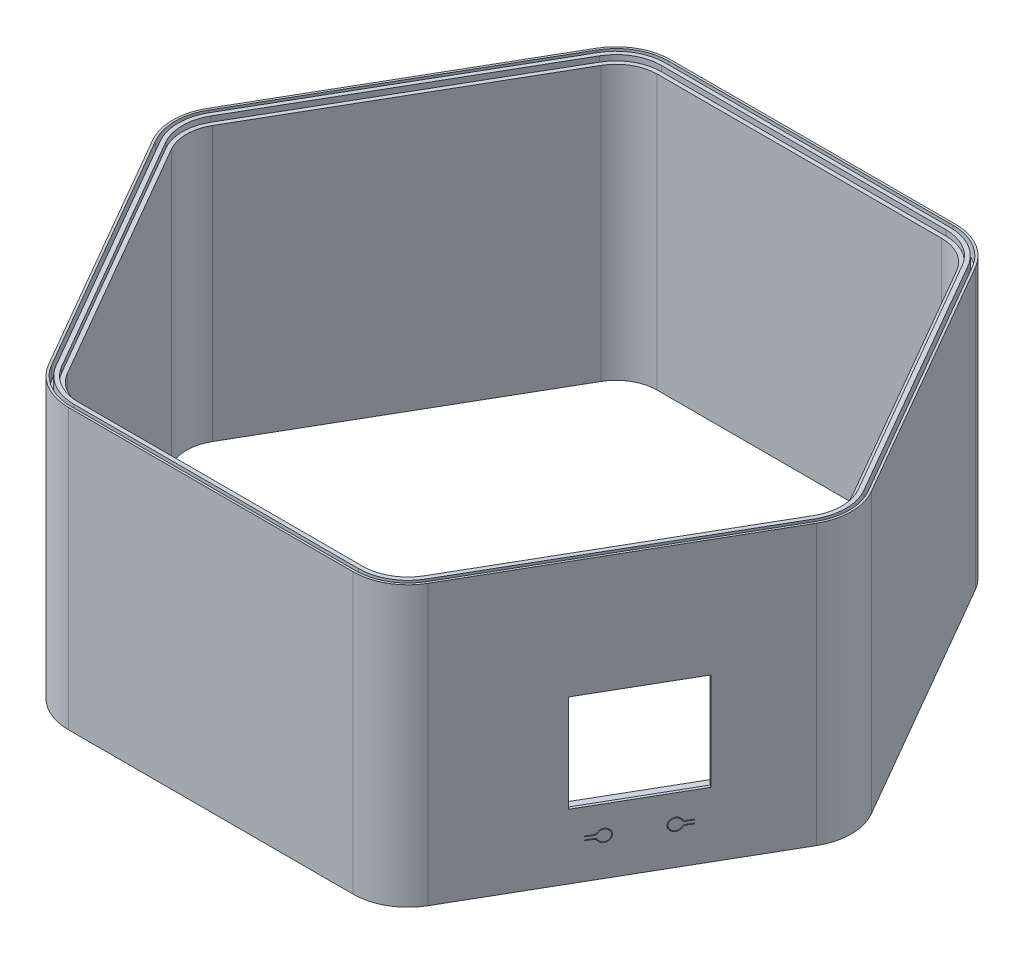
SolidWorks part; units mm, degrees
ref_plane "Front" through (0, 0, 0) normal (0, 0, 1) x (1, 0, 0)
ref_plane "Top" through (0, 0, 0) normal (0, 1, 0) x (1, 0, 0)
ref_plane "Right" through (0, 0, 0) normal (1, 0, 0) x (0, 0, -1)
sketch "Croquis1" plane through (0, 0, 0) normal (0, 1, 0) x (1, 0, 0)
  line L1 (-121.2436, -10) -> (-69.282, -100)
  line L2 (-51.9615, -110) -> (51.9615, -110)
  line L3 (69.282, -100) -> (121.2436, -10)
  line L4 (121.2436, 10) -> (69.282, 100)
  line L5 (51.9615, 110) -> (-51.9615, 110)
  line L6 (-69.282, 100) -> (-121.2436, 10)
  circle A0 centre (0, 0) radius 110 construction
  arc A1 (-69.282, 100) -> (-51.9615, 110) centre (-51.9615, 90) cw
  arc A2 (69.282, 100) -> (51.9615, 110) centre (51.9615, 90) ccw
  arc A3 (121.2436, -10) -> (121.2436, 10) centre (103.923, 0) ccw
  arc A4 (51.9615, -110) -> (69.282, -100) centre (51.9615, -90) ccw
  arc A5 (-69.282, -100) -> (-51.9615, -110) centre (-51.9615, -90) ccw
  arc A6 (-121.2436, -10) -> (-121.2436, 10) centre (-103.923, 0) cw
  dimension "D1" = 220
  dimension "D2" = 20
extrude "Saliente-Extruir1" add sketch "Croquis1" along normal blind 2
sketch "Croquis2" plane through (0, 2, 0) normal (0, 1, 0) x (1, 0, 0)
  line L6 (-64.9519, 97.5) -> (-116.9134, 7.5)
  line L7 (-116.9134, -7.5) -> (-64.9519, -97.5)
  line L8 (-51.9615, -105) -> (51.9615, -105)
  line L9 (64.9519, -97.5) -> (116.9134, -7.5)
  line L10 (116.9134, 7.5) -> (64.9519, 97.5)
  line L11 (51.9615, 105) -> (-51.9615, 105)
  line L12 (-69.282, 100) -> (-121.2436, 10)
  line L13 (-121.2436, -10) -> (-69.282, -100)
  line L14 (-51.9615, -110) -> (51.9615, -110)
  line L15 (69.282, -100) -> (121.2436, -10)
  line L16 (121.2436, 10) -> (69.282, 100)
  line L17 (51.9615, 110) -> (-51.9615, 110)
  line L18 (-69.282, 100) -> (-121.2436, 10)
  line L19 (-121.2436, -10) -> (-69.282, -100)
  line L20 (-51.9615, -110) -> (51.9615, -110)
  line L21 (69.282, -100) -> (121.2436, -10)
  line L22 (121.2436, 10) -> (69.282, 100)
  line L23 (51.9615, 110) -> (-51.9615, 110)
  arc A6 (-116.9134, 7.5) -> (-116.9134, -7.5) centre (-103.923, 0) ccw
  arc A7 (-64.9519, -97.5) -> (-51.9615, -105) centre (-51.9615, -90) ccw
  arc A8 (51.9615, -105) -> (64.9519, -97.5) centre (51.9615, -90) ccw
  arc A9 (116.9134, -7.5) -> (116.9134, 7.5) centre (103.923, 0) ccw
  arc A10 (64.9519, 97.5) -> (51.9615, 105) centre (51.9615, 90) ccw
  arc A11 (-51.9615, 105) -> (-64.9519, 97.5) centre (-51.9615, 90) ccw
  arc A12 (-51.9615, 110) -> (-69.282, 100) centre (-51.9615, 90) ccw
  arc A13 (-121.2436, 10) -> (-121.2436, -10) centre (-103.923, 0) ccw
  arc A14 (-69.282, -100) -> (-51.9615, -110) centre (-51.9615, -90) ccw
  arc A15 (51.9615, -110) -> (69.282, -100) centre (51.9615, -90) ccw
  arc A16 (121.2436, -10) -> (121.2436, 10) centre (103.923, 0) ccw
  arc A17 (69.282, 100) -> (51.9615, 110) centre (51.9615, 90) ccw
  arc A18 (-51.9615, 110) -> (-69.282, 100) centre (-51.9615, 90) ccw
  arc A19 (-121.2436, 10) -> (-121.2436, -10) centre (-103.923, 0) ccw
  arc A20 (-69.282, -100) -> (-51.9615, -110) centre (-51.9615, -90) ccw
  arc A21 (51.9615, -110) -> (69.282, -100) centre (51.9615, -90) ccw
  arc A22 (121.2436, -10) -> (121.2436, 10) centre (103.923, 0) ccw
  arc A23 (69.282, 100) -> (51.9615, 110) centre (51.9615, 90) ccw
  dimension "D1" = 0
  dimension "D2" = 5
extrude "Saliente-Extruir2" add sketch "Croquis2" along normal blind 100
sketch "Croquis3" plane through (90.9327, 0, 52.5) normal (-0.866, 0, -0.5) x (-0.5, 0, 0.866)
  line L0 (51.9615, 0) -> (-51.9615, 0) construction
  line L1 (22.0238, 60.6352) -> (22.0238, 22.4352)
  line L2 (22.0238, 60.6352) -> (-36.6762, 60.6352)
  line L3 (-36.6762, 60.6352) -> (-36.6762, 22.4352)
  line L4 (22.0238, 22.4352) -> (-36.6762, 22.4352)
  line L5 (-23.7762, 59.4352) -> (15.0238, 59.4352)
  line L6 (-23.7762, 59.4352) -> (-23.7762, 23.6352)
  line L7 (-23.7762, 23.6352) -> (15.0238, 23.6352)
  line L8 (15.0238, 59.4352) -> (15.0238, 23.6352)
  line L9 (51.9615, 102) -> (51.9615, 0) construction
  circle A0 centre (19.0238, 57.6352) radius 1.5
  circle A1 centre (19.0238, 25.4352) radius 1.5
  circle A2 centre (-33.6762, 25.4352) radius 1.5
  circle A3 centre (-33.6762, 57.6352) radius 1.5
  dimension "D1" = 3
  dimension "D2" = 3
  dimension "D3" = 58.7
  dimension "D4" = 3
  dimension "D5" = 3
  dimension "D6" = 3
  dimension "D7" = 3
  dimension "D8" = 3
  dimension "D9" = 3
  dimension "D10" = 3
  dimension "D11" = 38.2
  dimension "D12" = 35.8
  dimension "D13" = 38.8
  dimension "D14" = 1.2
  dimension "D15" = 7
  dimension "D16" = 23.6352
  dimension "D17" = 36.9377
extrude "Cortar-Extruir1" cut sketch "Croquis3" against normal blind 1
sketch "Croquis4" plane through (90.9327, 0, 52.5) normal (-0.866, 0, -0.5) x (-0.5, 0, 0.866)
  line L4 (15.0238, 59.4352) -> (-23.7762, 59.4352)
  line L5 (-23.7762, 59.4352) -> (-23.7762, 23.6352)
  line L6 (-23.7762, 23.6352) -> (15.0238, 23.6352)
  line L7 (15.0238, 23.6352) -> (15.0238, 59.4352)
  line L8 (14.4057, 59.1644) -> (-23.7762, 59.1644)
  line L9 (-23.7762, 59.1644) -> (-23.7762, 23.6352)
  line L10 (-23.7762, 23.6352) -> (14.4057, 23.6352)
  line L11 (14.4057, 23.6352) -> (14.4057, 59.1644)
  dimension "D1" = 0
extrude "Cortar-Extruir2" cut sketch "Croquis4" against normal blind 12
sketch "Croquis5" plane through (91.7987, 0, 53) normal (-0.866, 0, -0.5) x (-0.5, 0, 0.866)
  line L4 (22.0238, 60.6352) -> (-36.6762, 60.6352)
  line L5 (-36.6762, 60.6352) -> (-36.6762, 22.4352)
  line L6 (-36.6762, 22.4352) -> (22.0238, 22.4352)
  line L7 (22.0238, 22.4352) -> (22.0238, 60.6352)
  line L8 (22.0238, 60.6352) -> (-36.6762, 60.6352)
  line L9 (-36.6762, 60.6352) -> (-36.6762, 22.4352)
  line L10 (-36.6762, 22.4352) -> (22.0238, 22.4352)
  line L11 (22.0238, 22.4352) -> (22.0238, 60.6352)
  circle A0 centre (19.0238, 25.4352) radius 1.5 construction
  circle A1 centre (19.0238, 57.6352) radius 1.5 construction
  circle A2 centre (-33.6762, 57.6352) radius 1.5 construction
  circle A3 centre (-33.6762, 25.4352) radius 1.5 construction
  circle A4 centre (19.0238, 25.4352) radius 1.5
  circle A5 centre (19.0238, 57.6352) radius 1.5
  circle A6 centre (-33.6762, 57.6352) radius 1.5
  circle A7 centre (-33.6762, 25.4352) radius 1.5
  dimension "D1" = 0
extrude "Cortar-Extruir3" cut sketch "Croquis5" against normal blind 3
sketch "Croquis6" plane through (94.3968, 0, 54.5) normal (-0.866, 0, -0.5) x (-0.5, 0, 0.866)
  line L1 (-36.6762, 60.6352) -> (-31.6762, 60.6352)
  line L2 (-36.6762, 60.6352) -> (-36.6762, 55.6352)
  line L3 (-36.6762, 55.6352) -> (-32.6762, 55.6352)
  line L4 (-31.6762, 60.6352) -> (-31.6762, 56.6352)
  line L5 (-36.6762, 22.4352) -> (-31.6762, 22.4352)
  line L6 (-36.6762, 22.4352) -> (-36.6762, 27.4352)
  line L7 (-36.6762, 27.4352) -> (-32.6762, 27.4352)
  line L8 (-31.6762, 22.4352) -> (-31.6762, 26.4352)
  line L9 (22.0238, 22.4352) -> (17.0238, 22.4352)
  line L10 (22.0238, 22.4352) -> (22.0238, 27.4352)
  line L11 (22.0238, 27.4352) -> (18.0238, 27.4352)
  line L12 (17.0238, 22.4352) -> (17.0238, 26.4352)
  line L13 (22.0238, 60.6352) -> (17.0238, 60.6352)
  line L14 (22.0238, 60.6352) -> (22.0238, 55.6352)
  line L15 (22.0238, 55.6352) -> (18.0238, 55.6352)
  line L16 (17.0238, 60.6352) -> (17.0238, 56.6352)
  line L17 (-36.6762, 60.6352) -> (-36.6762, 22.4352) construction
  circle A2 centre (-33.6762, 25.4352) radius 1
  circle A4 centre (19.0238, 57.6352) radius 1
  circle A5 centre (19.0238, 25.4352) radius 1
  arc A6 (-32.6762, 55.6352) -> (-31.6762, 56.6352) centre (-32.6762, 56.6352) ccw
  arc A7 (-31.6762, 26.4352) -> (-32.6762, 27.4352) centre (-32.6762, 26.4352) ccw
  arc A8 (17.0238, 26.4352) -> (18.0238, 27.4352) centre (18.0238, 26.4352) cw
  arc A9 (18.0238, 55.6352) -> (17.0238, 56.6352) centre (18.0238, 56.6352) cw
  point P39 (-31.6762, 55.6352)
  dimension "D1" = 5
  dimension "D9" = 1
  dimension "D2" = 5
  dimension "D3" = 5
  dimension "D4" = 5
  dimension "D5" = 5
  dimension "D6" = 5
  dimension "D7" = 5
  dimension "D8" = 5
sketch "Croquis8" plane through (90.9327, 0, 52.5) normal (-0.866, 0, -0.5) x (-0.5, 0, 0.866)
  circle A0 centre (-33.6762, 57.6352) radius 1
  circle A1 centre (-33.6762, 25.4352) radius 1
  circle A2 centre (19.0238, 25.4352) radius 1
  circle A3 centre (19.0238, 57.6352) radius 1
extrude "Cortar-Extruir5" cut sketch "Croquis8" against normal up to surface (4 mm away) up to face at (98.0599, 41.5352, 48.1553)
sketch "Croquis11" plane through (0, 2, 0) normal (0, 1, 0) x (1, 0, 0)
  line L12 (51.9615, 105) -> (-51.9615, 105)
  line L13 (-64.9519, 97.5) -> (-116.9134, 7.5)
  line L14 (-116.9134, -7.5) -> (-64.9519, -97.5)
  line L15 (-51.9615, -105) -> (51.9615, -105)
  line L16 (64.9519, -97.5) -> (116.9134, -7.5)
  line L17 (116.9134, 7.5) -> (64.9519, 97.5)
  line L18 (51.9615, 105) -> (-51.9615, 105)
  line L19 (-64.9519, 97.5) -> (-116.9134, 7.5)
  line L20 (-116.9134, -7.5) -> (-64.9519, -97.5)
  line L21 (-51.9615, -105) -> (51.9615, -105)
  line L22 (64.9519, -97.5) -> (116.9134, -7.5)
  line L23 (116.9134, 7.5) -> (64.9519, 97.5)
  arc A12 (-51.9615, 105) -> (-64.9519, 97.5) centre (-51.9615, 90) ccw
  arc A13 (-116.9134, 7.5) -> (-116.9134, -7.5) centre (-103.923, 0) ccw
  arc A14 (-64.9519, -97.5) -> (-51.9615, -105) centre (-51.9615, -90) ccw
  arc A15 (51.9615, -105) -> (64.9519, -97.5) centre (51.9615, -90) ccw
  arc A16 (116.9134, -7.5) -> (116.9134, 7.5) centre (103.923, 0) ccw
  arc A17 (64.9519, 97.5) -> (51.9615, 105) centre (51.9615, 90) ccw
  arc A18 (-51.9615, 105) -> (-64.9519, 97.5) centre (-51.9615, 90) ccw
  arc A19 (-116.9134, 7.5) -> (-116.9134, -7.5) centre (-103.923, 0) ccw
  arc A20 (-64.9519, -97.5) -> (-51.9615, -105) centre (-51.9615, -90) ccw
  arc A21 (51.9615, -105) -> (64.9519, -97.5) centre (51.9615, -90) ccw
  arc A22 (116.9134, -7.5) -> (116.9134, 7.5) centre (103.923, 0) ccw
  arc A23 (64.9519, 97.5) -> (51.9615, 105) centre (51.9615, 90) ccw
  dimension "D1" = 0
extrude "Cortar-Extruir7" cut sketch "Croquis11" against normal blind 10
extrude "Saliente-Extruir3" add sketch "Croquis6" along normal blind 2.5
sketch "Croquis12" plane through (90.9327, 0, 52.5) normal (-0.866, 0, -0.5) x (-0.5, 0, 0.866)
  line L12 (14.4057, 59.1644) -> (14.4057, 23.6352)
  line L13 (14.4057, 23.6352) -> (15.0238, 23.6352)
  line L14 (15.0238, 23.6352) -> (15.0238, 59.4352)
  line L15 (15.0238, 59.4352) -> (-23.7762, 59.4352)
  line L16 (-23.7762, 59.4352) -> (-23.7762, 59.1644)
  line L17 (-23.7762, 59.1644) -> (14.4057, 59.1644)
  line L18 (14.4057, 59.1644) -> (14.4057, 23.6352)
  line L19 (14.4057, 23.6352) -> (15.0238, 23.6352)
  line L20 (15.0238, 23.6352) -> (15.0238, 59.4352)
  line L21 (15.0238, 59.4352) -> (-23.7762, 59.4352)
  line L22 (-23.7762, 59.4352) -> (-23.7762, 59.1644)
  line L23 (-23.7762, 59.1644) -> (14.4057, 59.1644)
  dimension "D1" = 0
extrude "Cortar-Extruir8" cut sketch "Croquis12" against normal blind 2
sketch "Croquis13" plane through (0, 102, 0) normal (0, 1, 0) x (1, 0, 0)
  line L12 (-66.2509, 98.25) -> (-118.2125, 8.25)
  line L13 (-118.2125, -8.25) -> (-66.2509, -98.25)
  line L14 (-51.9615, -106.5) -> (51.9615, -106.5)
  line L15 (66.2509, -98.25) -> (118.2125, -8.25)
  line L16 (118.2125, 8.25) -> (66.2509, 98.25)
  line L17 (51.9615, 106.5) -> (-51.9615, 106.5)
  line L18 (-66.2509, 98.25) -> (-118.2125, 8.25)
  line L19 (-118.2125, -8.25) -> (-66.2509, -98.25)
  line L20 (-51.9615, -106.5) -> (51.9615, -106.5)
  line L21 (66.2509, -98.25) -> (118.2125, -8.25)
  line L22 (118.2125, 8.25) -> (66.2509, 98.25)
  line L23 (51.9615, 106.5) -> (-51.9615, 106.5)
  arc A12 (-51.9615, 106.5) -> (-66.2509, 98.25) centre (-51.9615, 90) ccw
  arc A13 (-118.2125, 8.25) -> (-118.2125, -8.25) centre (-103.923, 0) ccw
  arc A14 (-66.2509, -98.25) -> (-51.9615, -106.5) centre (-51.9615, -90) ccw
  arc A15 (51.9615, -106.5) -> (66.2509, -98.25) centre (51.9615, -90) ccw
  arc A16 (118.2125, -8.25) -> (118.2125, 8.25) centre (103.923, 0) ccw
  arc A17 (66.2509, 98.25) -> (51.9615, 106.5) centre (51.9615, 90) ccw
  arc A18 (-51.9615, 106.5) -> (-66.2509, 98.25) centre (-51.9615, 90) ccw
  arc A19 (-118.2125, 8.25) -> (-118.2125, -8.25) centre (-103.923, 0) ccw
  arc A20 (-66.2509, -98.25) -> (-51.9615, -106.5) centre (-51.9615, -90) ccw
  arc A21 (51.9615, -106.5) -> (66.2509, -98.25) centre (51.9615, -90) ccw
  arc A22 (118.2125, -8.25) -> (118.2125, 8.25) centre (103.923, 0) ccw
  arc A23 (66.2509, 98.25) -> (51.9615, 106.5) centre (51.9615, 90) ccw
  dimension "D1" = 3.5
extrude "Cortar-Extruir9" cut sketch "Croquis13" against normal blind 2
sketch "Croquis14" plane through (95.2628, 0, 55) normal (0.866, 0, 0.5) x (0.5, 0, -0.866)
  line L0 (4.6852, 23.6352) -> (4.6852, 0) construction
  line L1 (23.7762, 23.6352) -> (-14.4057, 23.6352) construction
  line L2 (-51.9615, 0) -> (51.9615, 0) construction
  line L3 (23.7762, 13.6352) -> (4.6852, 13.6352) construction
  line L4 (-14.4057, 23.6352) -> (-14.4057, 13.6352) construction
  line L5 (23.7762, 23.6352) -> (23.7762, 13.6352) construction
  line L6 (4.6852, 13.6352) -> (-4.8602, 13.6352) construction
  line L7 (-4.8602, 13.6352) -> (-4.8602, 23.6352) construction
  line L8 (14.2307, 13.6352) -> (14.2307, 23.6352) construction
  line L9 (-7.4583, 14.1352) -> (-10.02, 14.1352)
  line L10 (-7.4583, 13.1352) -> (-10.02, 13.1352)
  line L11 (-7.5989, 14.3852) -> (-10.02, 14.3852)
  line L12 (-10.02, 14.1352) -> (-10.02, 13.1352)
  line L13 (-10.02, 14.3852) -> (-10.02, 12.8852)
  line L14 (-7.5989, 12.8852) -> (-10.02, 12.8852)
  line L15 (-7.5989, 14.3852) -> (-10.02, 14.3852)
  line L16 (16.2208, 13.6352) -> (19.3905, 13.6352) construction
  line L17 (-7.5989, 12.8852) -> (-10.02, 12.8852)
  line L18 (16.8288, 13.1352) -> (19.3905, 13.1352)
  line L19 (-7.4583, 14.1352) -> (-10.02, 14.1352)
  line L20 (16.8288, 14.1352) -> (19.3905, 14.1352)
  line L21 (-6.8504, 13.6352) -> (-10.02, 13.6352) construction
  line L22 (16.9693, 12.8852) -> (19.3905, 12.8852)
  line L23 (-7.4583, 13.1352) -> (-10.02, 13.1352)
  line L24 (16.9693, 14.3852) -> (19.3905, 14.3852)
  line L25 (16.9693, 12.8852) -> (19.3905, 12.8852)
  line L26 (19.3905, 14.3852) -> (19.3905, 12.8852)
  line L27 (19.3905, 14.1352) -> (19.3905, 13.1352)
  line L28 (16.9693, 14.3852) -> (19.3905, 14.3852)
  line L29 (16.8288, 13.1352) -> (19.3905, 13.1352)
  line L30 (16.8288, 14.1352) -> (19.3905, 14.1352)
  arc A0 (-6.7562, 12.4236) -> (-6.7562, 14.8467) centre (-4.8602, 13.6352) ccw
  arc A1 (-6.5923, 12.6352) -> (-6.5923, 14.6352) centre (-4.8602, 13.6352) ccw
  arc A2 (-6.5923, 12.6352) -> (-7.4583, 13.1352) centre (-7.4583, 12.1352) ccw
  arc A3 (-6.7562, 12.4236) -> (-7.5989, 12.8852) centre (-7.5989, 11.8852) ccw
  arc A4 (-6.7562, 14.8467) -> (-7.5989, 14.3852) centre (-7.5989, 15.3852) cw
  arc A5 (-6.5923, 14.6352) -> (-7.4583, 14.1352) centre (-7.4583, 15.1352) cw
  arc A6 (-6.5923, 12.6352) -> (-7.4583, 13.1352) centre (-7.4583, 12.1352) ccw
  arc A7 (-6.7562, 12.4236) -> (-7.5989, 12.8852) centre (-7.5989, 11.8852) ccw
  arc A8 (-6.7562, 14.8467) -> (-7.5989, 14.3852) centre (-7.5989, 15.3852) cw
  arc A9 (-6.5923, 14.6352) -> (-7.4583, 14.1352) centre (-7.4583, 15.1352) cw
  arc A10 (15.9628, 14.6352) -> (16.8288, 14.1352) centre (16.8288, 15.1352) ccw
  arc A11 (16.1267, 14.8467) -> (16.9693, 14.3852) centre (16.9693, 15.3852) ccw
  arc A12 (16.1267, 12.4236) -> (16.9693, 12.8852) centre (16.9693, 11.8852) cw
  arc A13 (15.9628, 12.6352) -> (16.8288, 13.1352) centre (16.8288, 12.1352) cw
  arc A14 (15.9628, 14.6352) -> (16.8288, 14.1352) centre (16.8288, 15.1352) ccw
  arc A15 (16.1267, 14.8467) -> (16.9693, 14.3852) centre (16.9693, 15.3852) ccw
  arc A16 (16.1267, 12.4236) -> (16.9693, 12.8852) centre (16.9693, 11.8852) cw
  arc A17 (15.9628, 12.6352) -> (16.8288, 13.1352) centre (16.8288, 12.1352) cw
  arc A18 (15.9628, 12.6352) -> (15.9628, 14.6352) centre (14.2307, 13.6352) cw
  arc A19 (16.1267, 12.4236) -> (16.1267, 14.8467) centre (14.2307, 13.6352) cw
  dimension "D4" = 1
  dimension "D5" = 1
extrude "Cortar-Extruir10" cut sketch "Croquis14" against normal blind 10 contours A19 A12 L22 L26 L18 A13 A18 A10 L20 L24 A11 | A5 A1 A2 L10 L13 L14 A3 A0 A4 L11 L9 region at (90.8932, 14.2219, 62.5683) region at (104.3176, 13.0485, 39.3166)
sketch "Croquis15" plane through (90.9327, 0, 52.5) normal (-0.866, 0, -0.5) x (-0.5, 0, 0.866)
  line L1 (-28.9649, 19.2891) -> (18.9862, 19.2891)
  line L2 (-28.9649, 19.2891) -> (-28.9649, 7.5308)
  line L3 (-28.9649, 7.5308) -> (18.9862, 7.5308)
  line L4 (18.9862, 19.2891) -> (18.9862, 7.5308)
extrude "Cortar-Extruir11" cut sketch "Croquis15" against normal blind 2.5
fillet "Redondeo1" radius 2 4 edges at (81.4396, 13.41, 68.9425) (105.4151, 13.41, 27.4157) (93.4273, 19.2891, 48.1791) (93.4273, 7.5308, 48.1791)
sketch "Croquis17" plane through (0, 0, 0) normal (0, -1, 0) x (1, 0, 0)
  line L12 (-51.9615, -108) -> (51.9615, -108)
  line L13 (67.55, -99) -> (119.5115, -9)
  line L14 (119.5115, 9) -> (67.55, 99)
  line L15 (51.9615, 108) -> (-51.9615, 108)
  line L16 (-67.55, 99) -> (-119.5115, 9)
  line L17 (-119.5115, -9) -> (-67.55, -99)
  line L18 (-51.9615, -108) -> (51.9615, -108)
  line L19 (67.55, -99) -> (119.5115, -9)
  line L20 (119.5115, 9) -> (67.55, 99)
  line L21 (51.9615, 108) -> (-51.9615, 108)
  line L22 (-67.55, 99) -> (-119.5115, 9)
  line L23 (-119.5115, -9) -> (-67.55, -99)
  line L31 (-51.9615, -106.8) -> (51.9615, -106.8)
  line L32 (66.5108, -98.4) -> (118.4723, -8.4)
  line L33 (118.4723, 8.4) -> (66.5108, 98.4)
  line L34 (51.9615, 106.8) -> (-51.9615, 106.8)
  line L35 (-66.5108, 98.4) -> (-118.4723, 8.4)
  line L36 (-118.4723, -8.4) -> (-66.5108, -98.4)
  line L37 (-51.9615, -106.8) -> (51.9615, -106.8)
  line L38 (66.5108, -98.4) -> (118.4723, -8.4)
  line L39 (118.4723, 8.4) -> (66.5108, 98.4)
  line L40 (51.9615, 106.8) -> (-51.9615, 106.8)
  line L41 (-66.5108, 98.4) -> (-118.4723, 8.4)
  line L42 (-118.4723, -8.4) -> (-66.5108, -98.4)
  arc A12 (-67.55, -99) -> (-51.9615, -108) centre (-51.9615, -90) ccw
  arc A13 (51.9615, -108) -> (67.55, -99) centre (51.9615, -90) ccw
  arc A14 (119.5115, -9) -> (119.5115, 9) centre (103.923, 0) ccw
  arc A15 (67.55, 99) -> (51.9615, 108) centre (51.9615, 90) ccw
  arc A16 (-51.9615, 108) -> (-67.55, 99) centre (-51.9615, 90) ccw
  arc A17 (-119.5115, 9) -> (-119.5115, -9) centre (-103.923, 0) ccw
  arc A18 (-67.55, -99) -> (-51.9615, -108) centre (-51.9615, -90) ccw
  arc A19 (51.9615, -108) -> (67.55, -99) centre (51.9615, -90) ccw
  arc A20 (119.5115, -9) -> (119.5115, 9) centre (103.923, 0) ccw
  arc A21 (67.55, 99) -> (51.9615, 108) centre (51.9615, 90) ccw
  arc A22 (-51.9615, 108) -> (-67.55, 99) centre (-51.9615, 90) ccw
  arc A23 (-119.5115, 9) -> (-119.5115, -9) centre (-103.923, 0) ccw
  arc A30 (-66.5108, -98.4) -> (-51.9615, -106.8) centre (-51.9615, -90) ccw
  arc A31 (51.9615, -106.8) -> (66.5108, -98.4) centre (51.9615, -90) ccw
  arc A32 (118.4723, -8.4) -> (118.4723, 8.4) centre (103.923, 0) ccw
  arc A33 (66.5108, 98.4) -> (51.9615, 106.8) centre (51.9615, 90) ccw
  arc A34 (-51.9615, 106.8) -> (-66.5108, 98.4) centre (-51.9615, 90) ccw
  arc A35 (-118.4723, 8.4) -> (-118.4723, -8.4) centre (-103.923, 0) ccw
  arc A36 (-66.5108, -98.4) -> (-51.9615, -106.8) centre (-51.9615, -90) ccw
  arc A37 (51.9615, -106.8) -> (66.5108, -98.4) centre (51.9615, -90) ccw
  arc A38 (118.4723, -8.4) -> (118.4723, 8.4) centre (103.923, 0) ccw
  arc A39 (66.5108, 98.4) -> (51.9615, 106.8) centre (51.9615, 90) ccw
  arc A40 (-51.9615, 106.8) -> (-66.5108, 98.4) centre (-51.9615, 90) ccw
  arc A41 (-118.4723, 8.4) -> (-118.4723, -8.4) centre (-103.923, 0) ccw
  dimension "D1" = 2
  dimension "D2" = 3.2
extrude "Cortar-Extruir12" cut sketch "Croquis17" against normal blind 5
sketch "Croquis18" plane through (0, 102, 0) normal (0, 1, 0) x (1, 0, 0)
  line L0 (51.9615, 109.2) -> (-51.9615, 109.2)
  line L1 (-68.5892, 99.6) -> (-120.5507, 9.6)
  line L2 (-120.5507, -9.6) -> (-68.5892, -99.6)
  line L3 (-51.9615, -109.2) -> (51.9615, -109.2)
  line L4 (68.5892, -99.6) -> (120.5507, -9.6)
  line L5 (120.5507, 9.6) -> (68.5892, 99.6)
  line L6 (51.9615, 108) -> (-51.9615, 108)
  line L7 (119.5115, 9) -> (67.55, 99)
  line L8 (67.55, -99) -> (119.5115, -9)
  line L9 (-51.9615, -108) -> (51.9615, -108)
  line L10 (-119.5115, -9) -> (-67.55, -99)
  line L11 (-67.55, 99) -> (-119.5115, 9)
  line L12 (51.9615, 108) -> (-51.9615, 108)
  line L13 (119.5115, 9) -> (67.55, 99)
  line L14 (67.55, -99) -> (119.5115, -9)
  line L15 (-51.9615, -108) -> (51.9615, -108)
  line L16 (-119.5115, -9) -> (-67.55, -99)
  line L17 (-67.55, 99) -> (-119.5115, 9)
  arc A0 (-51.9615, 109.2) -> (-68.5892, 99.6) centre (-51.9615, 90) ccw
  arc A1 (-120.5507, 9.6) -> (-120.5507, -9.6) centre (-103.923, 0) ccw
  arc A2 (-68.5892, -99.6) -> (-51.9615, -109.2) centre (-51.9615, -90) ccw
  arc A3 (51.9615, -109.2) -> (68.5892, -99.6) centre (51.9615, -90) ccw
  arc A4 (120.5507, -9.6) -> (120.5507, 9.6) centre (103.923, 0) ccw
  arc A5 (68.5892, 99.6) -> (51.9615, 109.2) centre (51.9615, 90) ccw
  arc A6 (-51.9615, 108) -> (-67.55, 99) centre (-51.9615, 90) ccw
  arc A7 (67.55, 99) -> (51.9615, 108) centre (51.9615, 90) ccw
  arc A8 (119.5115, -9) -> (119.5115, 9) centre (103.923, 0) ccw
  arc A9 (51.9615, -108) -> (67.55, -99) centre (51.9615, -90) ccw
  arc A10 (-67.55, -99) -> (-51.9615, -108) centre (-51.9615, -90) ccw
  arc A11 (-119.5115, 9) -> (-119.5115, -9) centre (-103.923, 0) ccw
  arc A12 (-51.9615, 108) -> (-67.55, 99) centre (-51.9615, 90) ccw
  arc A13 (67.55, 99) -> (51.9615, 108) centre (51.9615, 90) ccw
  arc A14 (119.5115, -9) -> (119.5115, 9) centre (103.923, 0) ccw
  arc A15 (51.9615, -108) -> (67.55, -99) centre (51.9615, -90) ccw
  arc A16 (-67.55, -99) -> (-51.9615, -108) centre (-51.9615, -90) ccw
  arc A17 (-119.5115, 9) -> (-119.5115, -9) centre (-103.923, 0) ccw
  dimension "D1" = 0
  dimension "D2" = 1.2
extrude "Cortar-Extruir13" cut sketch "Croquis18" against normal blind 5
